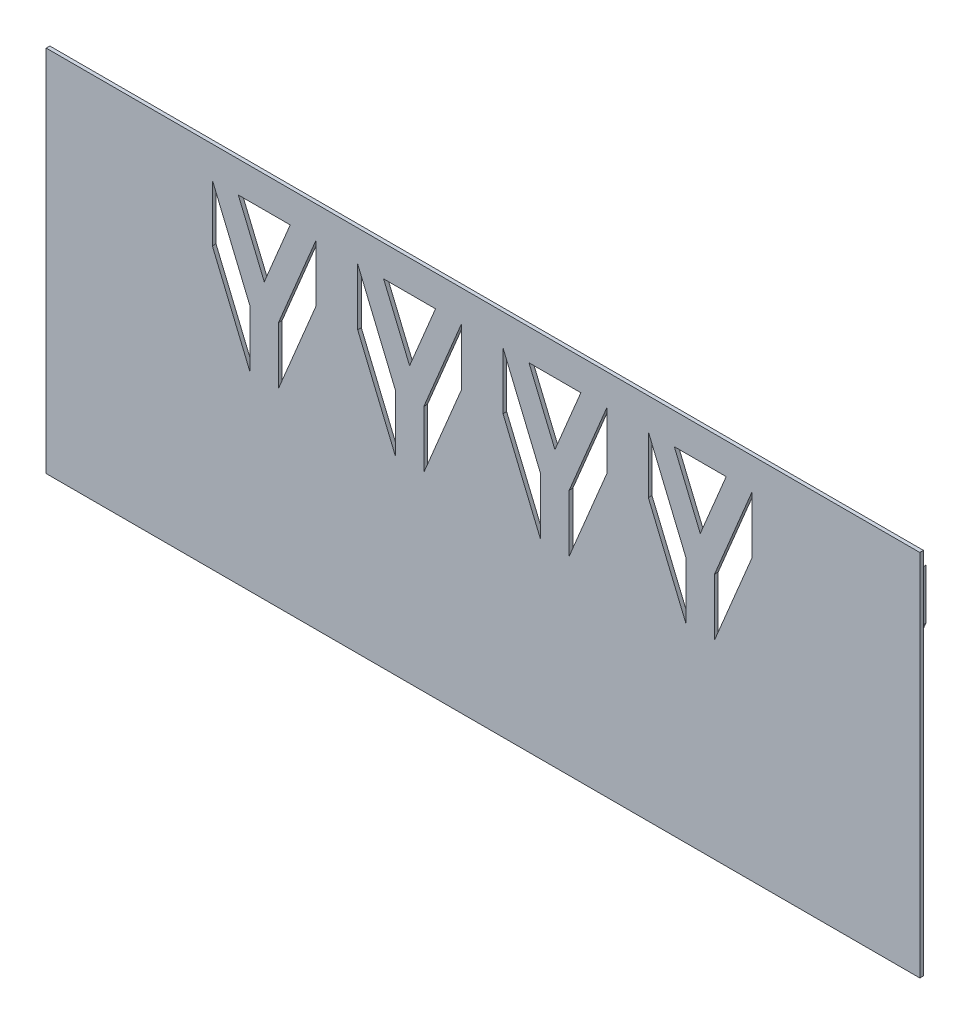
SolidWorks part; units mm, degrees
ref_plane "Front Plane" through (0, 0, 0) normal (0, 0, 1) x (1, 0, 0)
ref_plane "Top Plane" through (0, 0, 0) normal (0, 1, 0) x (1, 0, 0)
ref_plane "Right Plane" through (0, 0, 0) normal (1, 0, 0) x (0, 0, -1)
sketch "Sketch2" plane through (0, 0, 0) normal (0, 0, 1) x (1, 0, 0)
  line L1 (0, 0) -> (168.3109, 0)
  line L2 (0, 0) -> (0, -71)
  line L3 (0, -71) -> (168.3109, -71)
  line L4 (168.3109, 0) -> (168.3109, -71)
  line L30 (24.0048, -11.5) -> (32.0048, -11.5)
  line L52 (149.3798, -6.25) -> (154.0048, -17.35)
  line L65 (154.0048, -17.35) -> (158.6298, -6.25)
  line L75 (149.3798, -6.25) -> (158.6298, -6.25)
  line L84 (151.0048, -33.15) -> (151.0048, -23.45)
  line L96 (9.0048, -6) -> (19.0048, -6)
  line L97 (9.0048, -6) -> (14.0048, -18)
  line L98 (14.0048, -18) -> (19.0048, -6)
  line L99 (4.0048, -6) -> (4.0048, -17)
  line L100 (4.0048, -17) -> (11.2548, -34.4)
  line L101 (11.2548, -34.4) -> (11.2548, -23.4)
  line L102 (11.2548, -23.4) -> (4.0048, -6)
  line L103 (24.0048, -6) -> (24.0048, -17)
  line L104 (24.0048, -17) -> (16.7548, -34.4)
  line L105 (16.7548, -34.4) -> (16.7548, -23.4)
  line L106 (16.7548, -23.4) -> (24.0048, -6)
  line L109 (39.2548, -34.4) -> (39.2548, -23.4)
  line L110 (52.0048, -17) -> (44.7548, -34.4)
  line L111 (39.2548, -23.4) -> (32.0048, -6)
  line L112 (32.0048, -6) -> (32.0048, -17)
  line L113 (32.0048, -17) -> (39.2548, -34.4)
  line L114 (44.7548, -34.4) -> (44.7548, -23.4)
  line L115 (37.0048, -6) -> (42.0048, -18)
  line L116 (44.7548, -23.4) -> (52.0048, -6)
  line L117 (37.0048, -6) -> (47.0048, -6)
  line L118 (42.0048, -18) -> (47.0048, -6)
  line L119 (52.0048, -6) -> (52.0048, -17)
  line L123 (93.0048, -6) -> (103.0048, -6)
  line L124 (72.7548, -34.4) -> (72.7548, -23.4)
  line L126 (70.0048, -18) -> (75.0048, -6)
  line L127 (95.2548, -34.4) -> (95.2548, -23.4)
  line L128 (88.0048, -6) -> (88.0048, -17)
  line L129 (80.0048, -6) -> (80.0048, -17)
  line L130 (95.2548, -23.4) -> (88.0048, -6)
  line L131 (98.0048, -18) -> (103.0048, -6)
  line L132 (108.0048, -6) -> (108.0048, -17)
  line L133 (65.0048, -6) -> (70.0048, -18)
  line L134 (60.0048, -17) -> (67.2548, -34.4)
  line L135 (100.7548, -23.4) -> (108.0048, -6)
  line L138 (108.0048, -17) -> (100.7548, -34.4)
  line L139 (65.0048, -6) -> (75.0048, -6)
  line L141 (67.2548, -23.4) -> (60.0048, -6)
  line L142 (72.7548, -23.4) -> (80.0048, -6)
  line L143 (88.0048, -17) -> (95.2548, -34.4)
  line L144 (67.2548, -34.4) -> (67.2548, -23.4)
  line L145 (93.0048, -6) -> (98.0048, -18)
  line L146 (60.0048, -6) -> (60.0048, -17)
  line L147 (80.0048, -17) -> (72.7548, -34.4)
  line L148 (100.7548, -34.4) -> (100.7548, -23.4)
  line L149 (151.2548, -34.4) -> (151.2548, -23.4)
  line L150 (116.0048, -17) -> (123.2548, -34.4)
  line L151 (149.0048, -6) -> (154.0048, -18)
  line L152 (144.0048, -6) -> (144.0048, -17)
  line L153 (136.0048, -17) -> (128.7548, -34.4)
  line L154 (149.0048, -6) -> (159.0048, -6)
  line L155 (128.7548, -23.4) -> (136.0048, -6)
  line L156 (126.0048, -18) -> (131.0048, -6)
  line L157 (123.2548, -34.4) -> (123.2548, -23.4)
  line L158 (116.0048, -6) -> (116.0048, -17)
  line L159 (128.7548, -34.4) -> (128.7548, -23.4)
  line L160 (121.0048, -6) -> (126.0048, -18)
  line L161 (144.0048, -17) -> (151.2548, -34.4)
  line L162 (156.7548, -23.4) -> (164.0048, -6)
  line L163 (123.2548, -23.4) -> (116.0048, -6)
  line L164 (121.0048, -6) -> (131.0048, -6)
  line L165 (112, 0.1267) -> (116.0048, 0.1267)
  line L166 (154.0048, -18) -> (159.0048, -6)
  line L167 (136.0048, -6) -> (136.0048, -17)
  line L168 (151.2548, -23.4) -> (144.0048, -6)
  line L169 (156.7548, -34.4) -> (156.7548, -23.4)
  line L170 (151.0048, -23.45) -> (144.2548, -7.25)
  line L171 (144.2548, -7.25) -> (144.2548, -16.95)
  line L172 (164.0048, -6) -> (164.0048, -17)
  line L173 (164.0048, -17) -> (156.7548, -34.4)
  line L174 (144.2548, -16.95) -> (151.0048, -33.15)
  line L175 (157.0048, -23.45) -> (163.7548, -7.25)
  line L176 (163.7548, -7.25) -> (163.7548, -16.95)
  line L177 (163.7548, -16.95) -> (157.0048, -33.15)
  line L178 (157.0048, -33.15) -> (157.0048, -23.45)
  line L179 (9.3798, -6.25) -> (18.6298, -6.25)
  line L180 (14.0048, -17.35) -> (18.6298, -6.25)
  line L181 (9.3798, -6.25) -> (14.0048, -17.35)
  line L182 (4.2548, -7.25) -> (4.2548, -16.95)
  line L183 (4.2548, -16.95) -> (11.0048, -33.15)
  line L184 (11.0048, -33.15) -> (11.0048, -23.45)
  line L185 (11.0048, -23.45) -> (4.2548, -7.25)
  line L186 (23.7548, -7.25) -> (23.7548, -16.95)
  line L187 (23.7548, -16.95) -> (17.0048, -33.15)
  line L188 (17.0048, -33.15) -> (17.0048, -23.45)
  line L189 (17.0048, -23.45) -> (23.7548, -7.25)
  point P23 (14.0048, -6)
  point P42 (42.0048, -6)
  point P59 (70.0048, -6)
  point P74 (98.0048, -6)
  point P88 (126.0048, -6)
  point P103 (154.0048, -6)
  dimension "D1" = 168.3109
  dimension "D2" = 71
  dimension "D3" = 0.25
  dimension "D4" = 10
  dimension "D5" = 11
  dimension "D6" = 10
  dimension "D7" = 11
  dimension "D8" = 10
  dimension "D9" = 11
  dimension "D10" = 10
  dimension "D11" = 11
  dimension "D12" = 10
  dimension "D13" = 11
  dimension "D14" = 10
  dimension "D15" = 11
extrude "Boss-Extrude3" add sketch "Sketch2" along normal blind 0.7 contours L4 L1 L2 L3 L168 L149 L161 L152 L166 L151 L154 L163 L157 L150 L158 L146 L141 L144 L134 L145 L123 L131 L143 L128 L130 L127 L118 L115 L117 L113 L112 L103 L104 L105 L106 L111 L109 L102 | L151 L166 L154 | L149 L168 L152 L161 | L173 L172 L162 L169 | L101 L102 L99 L100 | L97 L98 L96 | L106 L105 L104 L103 | L175 L176 L177 L178 | L52 L65 L75 | L84 L170 L171 L174 | L179 L180 L181 | L182 L183 L184 L185 | L186 L187 L188 L189 region at (84.1741, -37.7404, 0) region at (23.9755, -14.25, 0) region at (14.0048, -6.1562, 0) region at (7.6028, -14.7113, 0) region at (147.6569, -25.6887, 0) region at (154.0048, -6.1562, 0) region at (160.4069, -14.7113, 0)
extrude "Boss-Extrude5" add sketch "Sketch2<6>" against normal blind 5 contours L179 L181 L180 | L184 L185 L182 L183 | L189 L188 L187 L186 | L75 L52 L65 | L171 L174 L84 L170 | L178 L177 L176 L175 region at (154.0048, -9.95, 0) region at (147.6298, -20.2, 0) region at (160.3798, -20.2, 0) region at (14.0048, -9.95, 0) region at (7.6298, -20.2, 0) region at (20.3798, -20.2, 0)
sketch "Sketch2<6>" plane through (0, 0, 0) normal (0, 0, 1) x (1, 0, 0) same geometry as "Sketch2"
